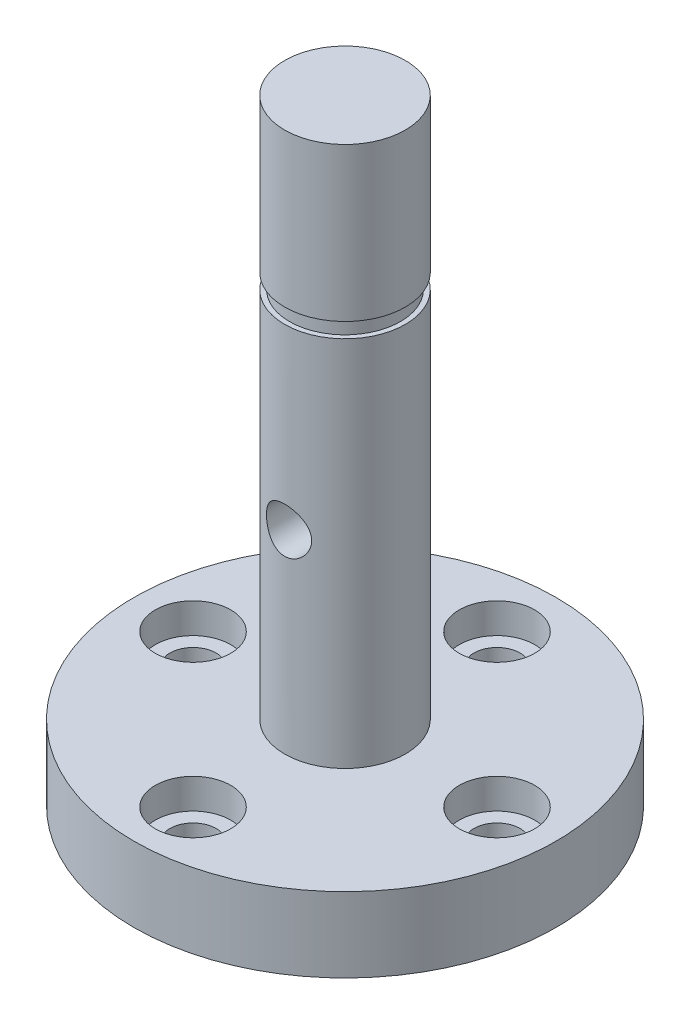
SolidWorks part; units mm, degrees
note: '?' marks a value the reader was unsure of.
other "Camera1"
material "6061-T6 (SS)"
ref_plane "Front Plane" through (0, 0, 0) normal (0, 0, 1) x (1, 0, 0)
ref_plane "Top Plane" through (0, 0, 0) normal (0, 1, 0) x (1, 0, 0)
ref_plane "Right Plane" through (0, 0, 0) normal (1, 0, 0) x (0, 0, -1)
sketch "Sketch1" plane through (0, 0, 0) normal (0, 1, 0) x (1, 0, 0)
  circle A0 centre (0, 0) radius 11.1125
  circle A1 centre (0, 0) radius 3.175 construction
  circle A2 centre (0, 0) radius 8 construction
  dimension "D1" = 6.35
  dimension "D2" = 16
  dimension "D3" = 22.225
extrude "Boss-Extrude1" add sketch "Sketch1" along normal blind 3.937
sketch "Sketch2" plane through (0, 3.937, 0) normal (0, 1, 0) x (1, 0, 0)
  circle A0 centre (0, 0) radius 3.175
  dimension "D1" = 6.35
extrude "Boss-Extrude2" add sketch "Sketch2" along normal blind 32.385 from surface at -3.937 starting at face at (0, 0, 11.1125)
hole_wizard "#2 Clearance Hole1" positions "Sketch3" profile "Sketch4" hole size "#2" standard "ANSI Inch" end condition through all
sketch "Sketch3" plane through (0, 3.937, 0) normal (0, 1, 0) x (1, 0, 0)
  circle A0 centre (0, 0) radius 8
  point P0 (0, -8)
  point P2 (0, 8)
  point P4 (-8, 0)
  point P6 (8, 0)
  dimension "D1" = 16
sketch "Sketch4" plane through (0, 3.937, 8) normal (1, 0, 0) x (0, 0, 1)
  line L0 (0, 0) -> (0, 3.937)
  line L1 (0, 3.937) -> (1.2192, 3.937)
  line L2 (1.2192, 3.937) -> (1.2192, 0)
  line L5 (1.2192, 0) -> (0, 0)
  line L11 (0, -6.35) -> (0, 107.95) construction
  dimension "Thru Hole Dia." = 2.4384
  dimension "Thru Hole Depth" = 3.937
sketch "Sketch5" plane through (0, 3.937, 0) normal (0, 1, 0) x (1, 0, 0)
  circle A0 centre (0, -8) radius 1.9844
  circle A1 centre (8, 0) radius 1.9844
  circle A2 centre (0, 8) radius 1.9844
  circle A3 centre (-8, 0) radius 1.9844
  dimension "D1" = 3.9688
extrude "Cut-Extrude1" cut sketch "Sketch5" against normal blind 1.5875
ref_plane "Plane1" through (0, 0, 3.175) normal (0, 0, 1) x (1, 0, 0)
hole_wizard "3/32 (0.09375) Diameter Hole1" positions "Sketch7" profile "Sketch8" hole size "3/32" standard "ANSI Inch" end condition through all
sketch "Sketch7" plane through (0, 0, 3.175) normal (0, 0, 1) x (1, 0, 0)
  line L0 (3.175, 3.937) -> (-3.175, 3.937) construction
  line L1 (3.175, 3.937) -> (-3.175, 3.937) construction
  line L2 (3.175, 32.385) -> (-3.175, 32.385) construction
  line L3 (3.175, 32.385) -> (-3.175, 32.385) construction
  line L4 (0, 32.385) -> (0, 3.937) construction
  line L6 (-11.1125, 0) -> (11.1125, 0) construction
  point P0 (0, 14.1446)
  dimension "D1" = 14.1446
sketch "Sketch8" plane through (0, 14.1446, 3.175) normal (1, 0, 0) x (0, -1, 0)
  line L0 (0, 0) -> (0, 14.2875)
  line L1 (0, 14.2875) -> (1.1906, 14.2875)
  line L2 (1.1906, 14.2875) -> (1.1906, 0)
  line L5 (1.1906, 0) -> (0, 0)
  line L11 (0, -6.35) -> (0, 107.95) construction
  dimension "Thru Hole Dia." = 2.3812
  dimension "Thru Hole Depth" = 14.2875
ref_axis "Axis1" through (0, 32.385, 0) along (0, -1, 0)?
ref_plane "Plane2" through (0, 0, 0) normal (1, 0, 0) x (0, 0, -1)
ref_plane "Plane3" through (0, 0, 0) normal (0, 0, 1) x (1, 0, 0)
sketch "Sketch9" plane through (0, 32.385, 0) normal (0, 1, 0) x (1, 0, 0)
  circle A0 centre (0, 0) radius 3.175
  circle A1 centre (0, 0) radius 2.921
  circle A2 centre (0, 0) radius 3.175 construction
  dimension "D1" = 5.842
extrude "Cut-Extrude2" cut sketch "Sketch9" along normal blind 0.7874 from offset 8.8582
